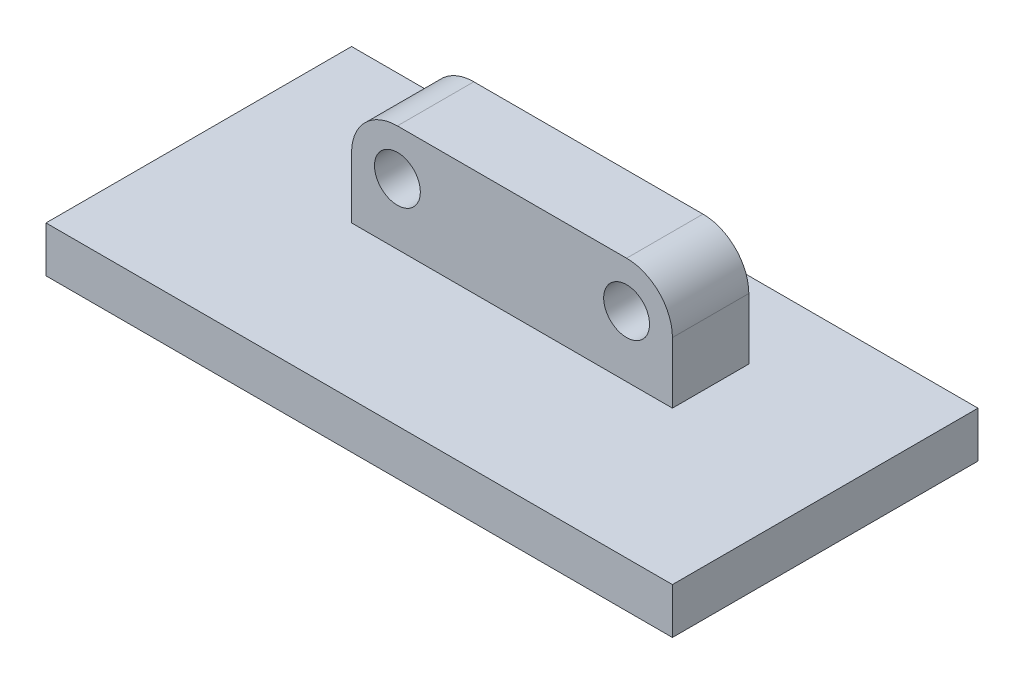
SolidWorks part; units mm, degrees
ref_plane "正面" through (0, 0, 0) normal (0, 0, 1) x (1, 0, 0)
ref_plane "平面" through (0, 0, 0) normal (0, 1, 0) x (1, 0, 0)
ref_plane "右側面" through (0, 0, 0) normal (1, 0, 0) x (0, 0, -1)
sketch "ｽｹｯﾁ1" plane through (0, 0, 0) normal (0, 0, 1) x (1, 0, 0)
  line L1 (-3, -4) -> (18, -4)
  line L2 (-3, -4) -> (-3, 0)
  line L3 (0, 3) -> (15, 3)
  line L4 (18, -4) -> (18, 0)
  circle A0 centre (0, 0) radius 1.5
  circle A1 centre (15, 0) radius 1.5
  arc A2 (15, 3) -> (18, 0) centre (15, 0) cw
  arc A3 (-3, 0) -> (0, 3) centre (0, 0) cw
  dimension "D1" = 3
  dimension "D2" = 15
  dimension "D3" = 3
  dimension "D4" = 4
extrude "ﾎﾞｽ - 押し出し1" add sketch "ｽｹｯﾁ1" along normal blind 5
sketch "ｽｹｯﾁ2" plane through (0, -4, 0) normal (0, -1, 0) x (1, 0, 0)
  line L0 (-3, 5) -> (18, 5) construction
  line L1 (-13, -5) -> (28, -5)
  line L2 (-13, -5) -> (-13, 15)
  line L3 (-13, 15) -> (28, 15)
  line L4 (28, -5) -> (28, 15)
  line L5 (-3, 0) -> (18, 0) construction
  line L6 (-3, 5) -> (-3, 0) construction
  line L7 (18, 5) -> (18, 0) construction
  dimension "D1" = 5
  dimension "D2" = 10
  dimension "D3" = 10
  dimension "D4" = 10
extrude "ﾎﾞｽ - 押し出し2" add sketch "ｽｹｯﾁ2" along normal blind 3
